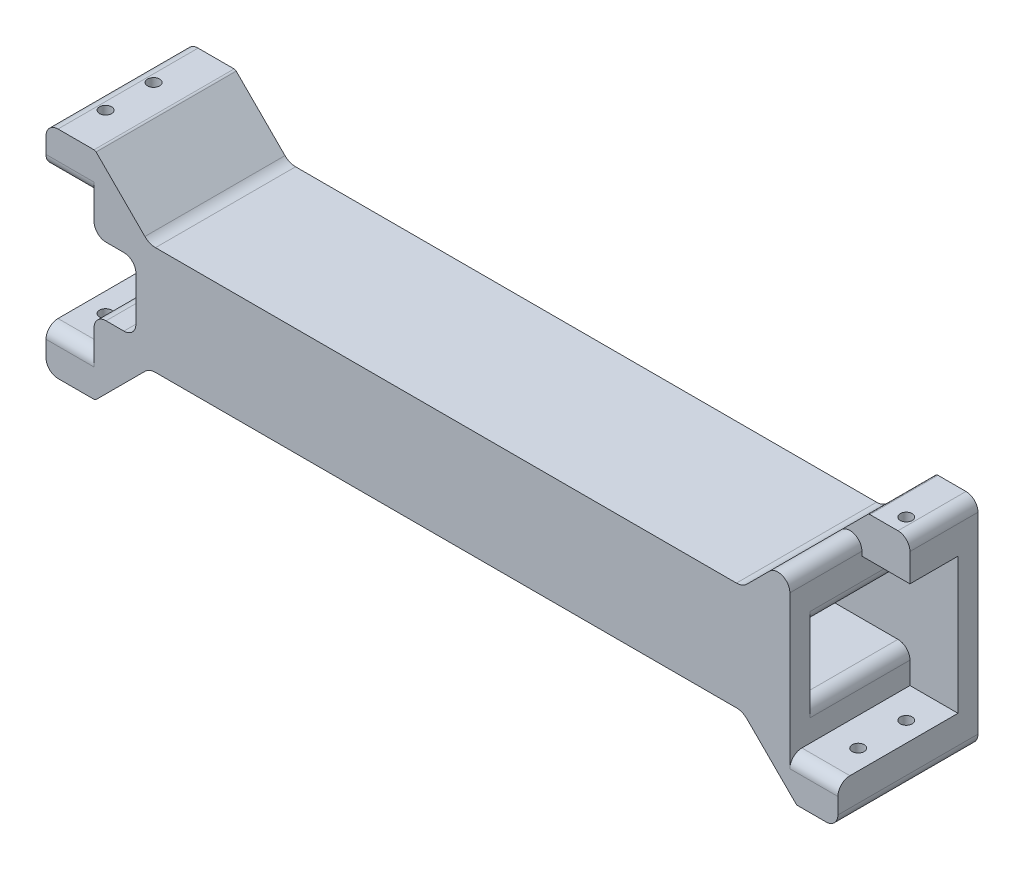
SolidWorks part; units mm, degrees
ref_plane "前视基准面" through (0, 0, 0) normal (0, 0, 1) x (1, 0, 0)
ref_plane "上视基准面" through (0, 0, 0) normal (0, 1, 0) x (1, 0, 0)
ref_plane "右视基准面" through (0, 0, 0) normal (1, 0, 0) x (0, 0, -1)
other "Configuration Table"
sketch "草图1" plane through (0, 0, 0) normal (0, 0, 1) x (1, 0, 0)
  line L0 (49.1217, 60) -> (0, 60) construction
  line L1 (0, 60) -> (0, 57) construction
  line L2 (0, 57) -> (49.1217, 57) construction
  line L3 (63.9537, 46.7157) -> (51.7639, 58.9056) construction
  line L4 (49.6425, 56.7843) -> (61.8324, 44.5944) construction
  line L5 (49.1217, 3) -> (0, 3) construction
  line L6 (0, 3) -> (0, 0) construction
  line L7 (0, 0) -> (49.1217, 0) construction
  line L8 (61.8324, 15.4056) -> (49.6425, 3.2157) construction
  line L9 (51.7639, 1.0944) -> (63.9537, 13.2843) construction
  line L10 (64.4745, 43.5) -> (209.6217, 43.5) construction
  line L11 (209.6217, 46.5) -> (64.4745, 46.5) construction
  line L12 (212.2639, 44.5944) -> (224.4537, 56.7843) construction
  line L13 (222.3324, 58.9056) -> (210.1425, 46.7157) construction
  line L14 (224.9745, 57) -> (268.4745, 57) construction
  line L15 (268.4745, 57) -> (268.4745, 60) construction
  line L16 (268.4745, 60) -> (224.9745, 60) construction
  line L17 (64.4745, 13.5) -> (209.6217, 13.5) construction
  line L18 (209.6217, 16.5) -> (64.4745, 16.5) construction
  line L19 (210.1425, 13.2843) -> (222.3324, 1.0944) construction
  line L20 (224.4537, 3.2157) -> (212.2639, 15.4056) construction
  line L21 (224.9745, 0) -> (268.4745, 0) construction
  line L22 (268.4745, 0) -> (268.4745, 3) construction
  line L23 (268.4745, 3) -> (224.9745, 3) construction
  line L24 (49.1217, 60) -> (0, 60)
  line L25 (0, 60) -> (0, 57)
  line L26 (0, 57) -> (49.1217, 57)
  line L27 (63.9537, 46.7157) -> (51.7639, 58.9056)
  line L28 (49.6425, 56.7843) -> (61.8324, 44.5944)
  line L29 (49.1217, 3) -> (0, 3)
  line L30 (0, 3) -> (0, 0)
  line L31 (0, 0) -> (49.1217, 0)
  line L32 (61.8324, 15.4056) -> (49.6425, 3.2157)
  line L33 (51.7639, 1.0944) -> (63.9537, 13.2843)
  line L34 (64.4745, 43.5) -> (209.6217, 43.5)
  line L35 (209.6217, 46.5) -> (64.4745, 46.5)
  line L36 (212.2639, 44.5944) -> (224.4537, 56.7843)
  line L37 (222.3324, 58.9056) -> (210.1425, 46.7157)
  line L38 (224.9745, 57) -> (268.4745, 57)
  line L39 (268.4745, 57) -> (268.4745, 60)
  line L40 (268.4745, 60) -> (224.9745, 60)
  line L41 (64.4745, 13.5) -> (209.6217, 13.5)
  line L42 (209.6217, 16.5) -> (64.4745, 16.5)
  line L43 (210.1425, 13.2843) -> (222.3324, 1.0944)
  line L44 (224.4537, 3.2157) -> (212.2639, 15.4056)
  line L45 (224.9745, 0) -> (268.4745, 0)
  line L46 (268.4745, 0) -> (268.4745, 3)
  line L47 (268.4745, 3) -> (224.9745, 3)
  line L48 (234.9745, 3) -> (234.9745, 57)
  line L49 (37.1217, 3) -> (37.1217, 57)
  arc A0 (49.6425, 56.7843) -> (49.1217, 57) centre (49.1217, 56.2634) ccw construction
  arc A1 (51.7639, 58.9056) -> (49.1217, 60) centre (49.1217, 56.2634) ccw construction
  arc A2 (61.8324, 44.5944) -> (64.4745, 43.5) centre (64.4745, 47.2366) ccw construction
  arc A3 (63.9537, 46.7157) -> (64.4745, 46.5) centre (64.4745, 47.2366) ccw construction
  arc A4 (49.1217, 0) -> (51.7639, 1.0944) centre (49.1217, 3.7366) ccw construction
  arc A5 (49.1217, 3) -> (49.6425, 3.2157) centre (49.1217, 3.7366) ccw construction
  arc A6 (64.4745, 13.5) -> (63.9537, 13.2843) centre (64.4745, 12.7634) ccw construction
  arc A7 (64.4745, 16.5) -> (61.8324, 15.4056) centre (64.4745, 12.7634) ccw construction
  arc A8 (209.6217, 43.5) -> (212.2639, 44.5944) centre (209.6217, 47.2366) ccw construction
  arc A9 (209.6217, 46.5) -> (210.1425, 46.7157) centre (209.6217, 47.2366) ccw construction
  arc A10 (224.9745, 57) -> (224.4537, 56.7843) centre (224.9745, 56.2634) ccw construction
  arc A11 (224.9745, 60) -> (222.3324, 58.9056) centre (224.9745, 56.2634) ccw construction
  arc A12 (210.1425, 13.2843) -> (209.6217, 13.5) centre (209.6217, 12.7634) ccw construction
  arc A13 (212.2639, 15.4056) -> (209.6217, 16.5) centre (209.6217, 12.7634) ccw construction
  arc A14 (222.3324, 1.0944) -> (224.9745, 0) centre (224.9745, 3.7366) ccw construction
  arc A15 (224.4537, 3.2157) -> (224.9745, 3) centre (224.9745, 3.7366) ccw construction
  arc A16 (49.6425, 56.7843) -> (49.1217, 57) centre (49.1217, 56.2634) ccw
  arc A17 (51.7639, 58.9056) -> (49.1217, 60) centre (49.1217, 56.2634) ccw
  arc A18 (61.8324, 44.5944) -> (64.4745, 43.5) centre (64.4745, 47.2366) ccw
  arc A19 (63.9537, 46.7157) -> (64.4745, 46.5) centre (64.4745, 47.2366) ccw
  arc A20 (49.1217, 0) -> (51.7639, 1.0944) centre (49.1217, 3.7366) ccw
  arc A21 (49.1217, 3) -> (49.6425, 3.2157) centre (49.1217, 3.7366) ccw
  arc A22 (64.4745, 13.5) -> (63.9537, 13.2843) centre (64.4745, 12.7634) ccw
  arc A23 (64.4745, 16.5) -> (61.8324, 15.4056) centre (64.4745, 12.7634) ccw
  arc A24 (209.6217, 43.5) -> (212.2639, 44.5944) centre (209.6217, 47.2366) ccw
  arc A25 (209.6217, 46.5) -> (210.1425, 46.7157) centre (209.6217, 47.2366) ccw
  arc A26 (224.9745, 57) -> (224.4537, 56.7843) centre (224.9745, 56.2634) ccw
  arc A27 (224.9745, 60) -> (222.3324, 58.9056) centre (224.9745, 56.2634) ccw
  arc A28 (210.1425, 13.2843) -> (209.6217, 13.5) centre (209.6217, 12.7634) ccw
  arc A29 (212.2639, 15.4056) -> (209.6217, 16.5) centre (209.6217, 12.7634) ccw
  arc A30 (222.3324, 1.0944) -> (224.9745, 0) centre (224.9745, 3.7366) ccw
  arc A31 (224.4537, 3.2157) -> (224.9745, 3) centre (224.9745, 3.7366) ccw
  dimension "D1" = 10
  dimension "D2" = 12
extrude "凸台-拉伸1" add sketch "草图1" against normal blind 35 contours L44 A31 L47 L48 L38 A26 L36 A24 L34 A18 L28 A16 L26 L49 L29 A21 L32 A23 L42 A29 region at (135.3571, 30, 0)
sketch "草图2" plane through (37.1217, 0, 0) normal (-1, 0, 0) x (0, 0, 1)
  line L0 (-35, 43.5) -> (0, 43.5) construction
  line L1 (-35, 43.5) -> (0, 43.5)
  line L2 (-35, 16.5) -> (0, 16.5) construction
  line L3 (-35, 16.5) -> (0, 16.5)
  line L4 (-35, 43.5) -> (0, 16.5) construction
  line L5 (-35, 16.5) -> (0, 43.5) construction
  line L6 (0, 3) -> (0, 57) construction
  line L7 (-30, 38.5) -> (-5, 38.5)
  line L8 (-30, 38.5) -> (-30, 21.5)
  line L9 (-30, 21.5) -> (-5, 21.5)
  line L10 (-5, 38.5) -> (-5, 21.5)
  line L11 (-30, 38.5) -> (-5, 21.5) construction
  line L12 (-30, 21.5) -> (-5, 38.5) construction
  point P4 (-17.5, 30)
  dimension "D1" = 5
  dimension "D2" = 5
extrude "切除-拉伸1" cut sketch "草图2" against normal through all contours L10 L7 L8 L9 region at (37.1217, 30, -17.5)
sketch "草图3" plane through (37.1217, 0, 0) normal (-1, 0, 0) x (0, 0, 1)
  line L0 (-30, 52) -> (-30, 8)
  line L1 (-30, 8) -> (-5, 8)
  line L2 (-5, 8) -> (-5, 52)
  line L3 (-5, 52) -> (-30, 52)
  line L4 (0, 3) -> (0, 57)
  line L5 (0, 57) -> (-35, 57)
  line L6 (-35, 57) -> (-35, 3)
  line L7 (-35, 3) -> (0, 3)
  line L8 (0, 3) -> (0, 57)
  line L9 (0, 57) -> (-35, 57)
  line L10 (-35, 57) -> (-35, 3)
  line L11 (-35, 3) -> (0, 3)
  line L12 (-30, 47) -> (-5, 47)
  line L13 (-30, 13) -> (-5, 13)
  line M14 (-5, 21.5) -> (-30, 21.5)
  line M16 (-30, 38.5) -> (-5, 38.5)
  dimension "D3" = 5
  dimension "D4" = 5
  dimension "D1" = 0
  dimension "D2" = 5
extrude "切除-拉伸2" cut sketch "草图3" against normal blind 12 contours L12 L0 L2 M16 | L0 L13 L2 M14 region at (37.1217, 42.75, -17.5) region at (37.1217, 17.25, -17.5)
ref_plane "基准面1" through (136.0481, 0, 0) normal (-1, 0, 0) x (0, 0, 1)
mirror "镜向1" about plane through (136.0481, 0, 0) normal (-1, 0, 0) of "切除-拉伸2"
fillet "圆角1" radius 3 8 edges at (222.9745, 38.5, -17.5) (222.9745, 21.5, -17.5) (234.9745, 57, -17.5) (234.9745, 3, -17.5) (37.1217, 57, -17.5) (37.1217, 3, -17.5) (49.1217, 21.5, -17.5) (49.1217, 38.5, -17.5)
sketch "草图4" plane through (0, 57, 0) normal (0, 1, 0) x (1, 0, 0)
  circle A2 centre (42, 22) radius 1.5 construction
  circle A3 centre (42, 10) radius 1.5 construction
  circle A6 centre (42, 22) radius 1.5
  circle A7 centre (42, 10) radius 1.5
  circle A8 centre (230.0481, 22) radius 1.5 construction
  circle A9 centre (230.0481, 10) radius 1.5 construction
  circle A10 centre (230.0481, 22) radius 1.5
  circle A11 centre (230.0481, 10) radius 1.5
extrude "切除-拉伸3" cut sketch "草图4" against normal through all both and the other way through all
sketch "草图5" plane through (0, 0, -5) normal (0, 0, -1) x (-1, 0, 0)
  line L0 (-222.9745, 41.5) -> (-222.9745, 18.5)
  line L1 (-49.1217, 41.5) -> (-49.1217, 18.5)
  line L12 (-37.1217, 13) -> (-37.1217, 47)
  line L13 (-37.1217, 47) -> (-49.1217, 47)
  line L14 (-49.1217, 47) -> (-49.1217, 41.5)
  line L15 (-52.1217, 38.5) -> (-219.9745, 38.5)
  line L16 (-222.9745, 41.5) -> (-222.9745, 47)
  line L17 (-222.9745, 47) -> (-234.9745, 47)
  line L18 (-234.9745, 47) -> (-234.9745, 13)
  line L19 (-234.9745, 13) -> (-222.9745, 13)
  line L20 (-222.9745, 13) -> (-222.9745, 18.5)
  line L21 (-219.9745, 21.5) -> (-52.1217, 21.5)
  line L22 (-49.1217, 18.5) -> (-49.1217, 13)
  line L23 (-49.1217, 13) -> (-37.1217, 13)
  line L24 (-37.1217, 13) -> (-37.1217, 47)
  line L25 (-37.1217, 47) -> (-49.1217, 47)
  line L26 (-49.1217, 47) -> (-49.1217, 41.5)
  line L27 (-52.1217, 38.5) -> (-219.9745, 38.5)
  line L28 (-222.9745, 41.5) -> (-222.9745, 47)
  line L29 (-222.9745, 47) -> (-234.9745, 47)
  line L30 (-234.9745, 47) -> (-234.9745, 13)
  line L31 (-234.9745, 13) -> (-222.9745, 13)
  line L32 (-222.9745, 13) -> (-222.9745, 18.5)
  line L33 (-219.9745, 21.5) -> (-52.1217, 21.5)
  line L34 (-49.1217, 18.5) -> (-49.1217, 13)
  line L35 (-49.1217, 13) -> (-37.1217, 13)
  arc A4 (-52.1217, 38.5) -> (-49.1217, 41.5) centre (-52.1217, 41.5) ccw
  arc A5 (-222.9745, 41.5) -> (-219.9745, 38.5) centre (-219.9745, 41.5) ccw
  arc A6 (-219.9745, 21.5) -> (-222.9745, 18.5) centre (-219.9745, 18.5) ccw
  arc A7 (-49.1217, 18.5) -> (-52.1217, 21.5) centre (-52.1217, 18.5) ccw
  arc A8 (-52.1217, 38.5) -> (-49.1217, 41.5) centre (-52.1217, 41.5) ccw
  arc A9 (-222.9745, 41.5) -> (-219.9745, 38.5) centre (-219.9745, 41.5) ccw
  arc A10 (-219.9745, 21.5) -> (-222.9745, 18.5) centre (-219.9745, 18.5) ccw
  arc A11 (-49.1217, 18.5) -> (-52.1217, 21.5) centre (-52.1217, 18.5) ccw
  line M17 (-37.1217, 13) -> (-37.1217, 47)
  line M18 (-37.1217, 47) -> (-49.1217, 47)
  line M19 (-49.1217, 47) -> (-49.1217, 41.5)
  line M23 (-222.9745, 41.5) -> (-222.9745, 47)
  line M24 (-222.9745, 47) -> (-234.9745, 47)
  line M25 (-234.9745, 47) -> (-234.9745, 13)
  line M26 (-234.9745, 13) -> (-222.9745, 13)
  line M27 (-222.9745, 13) -> (-222.9745, 18.5)
  line M31 (-49.1217, 18.5) -> (-49.1217, 13)
  line M32 (-49.1217, 13) -> (-37.1217, 13)
  dimension "D1" = 0
extrude "切除-拉伸4" cut sketch "草图5" against normal blind 10 contours L0 M23 M24 M25 M26 M27 | L1 M19 M31 M32 M17 M18 region at (228.9745, 30, -5) region at (43.1217, 30, -5)
fillet "圆角2" radius 3 4 edges at (228.9745, 13, 0) (228.9745, 47, 0) (43.1217, 13, 0) (43.1217, 47, 0)
sketch "草图6" plane through (0, 16.5, 0) normal (0, -1, 0) x (1, 0, 0)
  line L0 (106.0481, -17.5) -> (166.0481, -17.5) construction
  line L1 (136.0481, 19.25) -> (136.0481, -19.25) construction
  line L2 (106.0481, -9.5) -> (166.0481, -9.5)
  line L3 (106.0481, -25.5) -> (166.0481, -25.5)
  line L4 (136.0481, 0) -> (136.0481, -35)
  line L5 (209.6217, 0) -> (64.4745, 0) construction
  line L6 (209.6217, -35) -> (64.4745, -35) construction
  arc A0 (106.0481, -9.5) -> (106.0481, -25.5) centre (106.0481, -17.5) ccw
  arc A1 (166.0481, -25.5) -> (166.0481, -9.5) centre (166.0481, -17.5) ccw
  point P4 (136.0481, -17.5)
  dimension "D2" = 8
  dimension "D1" = 60
extrude "切除-拉伸5" [suppressed] cut sketch "草图6" against normal through all contours L3 A1 L2 L4 | L2 A0 L3 L4
sketch "草图7" plane through (0, 0, 0) normal (0, 0, 1) x (1, 0, 0)
  line L0 (234.9745, 47) -> (234.9745, 50) construction
  line L1 (222.9745, 47) -> (222.9745, 50) construction
  line L2 (222.9745, 47) -> (234.9745, 47) construction
  line L3 (49.1217, 50) -> (49.1217, 10) construction
  line L4 (49.1217, 10) -> (37.1217, 10) construction
  line L5 (37.1217, 10) -> (37.1217, 6) construction
  line L6 (40.1217, 3) -> (49.1217, 3) construction
  line L7 (49.6425, 3.2157) -> (61.8324, 15.4056) construction
  line L8 (64.4745, 16.5) -> (209.6217, 16.5) construction
  line L9 (212.2639, 15.4056) -> (224.4537, 3.2157) construction
  line L10 (224.9745, 3) -> (231.9745, 3) construction
  line L11 (234.9745, 6) -> (234.9745, 10) construction
  line L12 (234.9745, 10) -> (222.9745, 10) construction
  line L13 (222.9745, 10) -> (222.9745, 50) construction
  line L14 (234.9745, 50) -> (234.9745, 54) construction
  line L15 (231.9745, 57) -> (224.9745, 57) construction
  line L16 (224.4537, 56.7843) -> (212.2639, 44.5944) construction
  line L17 (209.6217, 43.5) -> (64.4745, 43.5) construction
  line L18 (61.8324, 44.5944) -> (49.6425, 56.7843) construction
  line L19 (49.1217, 57) -> (40.1217, 57) construction
  line L20 (37.1217, 54) -> (37.1217, 50) construction
  line L21 (37.1217, 50) -> (49.1217, 50) construction
  line L22 (234.9745, 47) -> (234.9745, 50)
  line L23 (222.9745, 47) -> (222.9745, 50)
  line L24 (222.9745, 47) -> (234.9745, 47)
  line L25 (49.1217, 50) -> (49.1217, 10)
  line L26 (49.1217, 10) -> (37.1217, 10)
  line L27 (37.1217, 10) -> (37.1217, 6)
  line L28 (40.1217, 3) -> (49.1217, 3)
  line L29 (49.6425, 3.2157) -> (61.8324, 15.4056)
  line L30 (64.4745, 16.5) -> (209.6217, 16.5)
  line L31 (212.2639, 15.4056) -> (224.4537, 3.2157)
  line L32 (224.9745, 3) -> (231.9745, 3)
  line L33 (234.9745, 6) -> (234.9745, 10)
  line L34 (234.9745, 10) -> (222.9745, 10)
  line L35 (222.9745, 10) -> (222.9745, 50)
  line L36 (234.9745, 50) -> (234.9745, 54)
  line L37 (231.9745, 57) -> (224.9745, 57)
  line L38 (224.4537, 56.7843) -> (212.2639, 44.5944)
  line L39 (209.6217, 43.5) -> (64.4745, 43.5)
  line L40 (61.8324, 44.5944) -> (49.6425, 56.7843)
  line L41 (49.1217, 57) -> (40.1217, 57)
  line L42 (37.1217, 54) -> (37.1217, 50)
  line L43 (37.1217, 50) -> (49.1217, 50)
  line L44 (222.9745, 50) -> (222.9745, 55.3051)
  arc A0 (37.1217, 6) -> (40.1217, 3) centre (40.1217, 6) ccw construction
  arc A1 (49.1217, 3) -> (49.6425, 3.2157) centre (49.1217, 3.7366) ccw construction
  arc A2 (64.4745, 16.5) -> (61.8324, 15.4056) centre (64.4745, 12.7634) ccw construction
  arc A3 (212.2639, 15.4056) -> (209.6217, 16.5) centre (209.6217, 12.7634) ccw construction
  arc A4 (224.4537, 3.2157) -> (224.9745, 3) centre (224.9745, 3.7366) ccw construction
  arc A5 (231.9745, 3) -> (234.9745, 6) centre (231.9745, 6) ccw construction
  arc A6 (234.9745, 54) -> (231.9745, 57) centre (231.9745, 54) ccw construction
  arc A7 (224.9745, 57) -> (224.4537, 56.7843) centre (224.9745, 56.2634) ccw construction
  arc A8 (209.6217, 43.5) -> (212.2639, 44.5944) centre (209.6217, 47.2366) ccw construction
  arc A9 (61.8324, 44.5944) -> (64.4745, 43.5) centre (64.4745, 47.2366) ccw construction
  arc A10 (49.6425, 56.7843) -> (49.1217, 57) centre (49.1217, 56.2634) ccw construction
  arc A11 (40.1217, 57) -> (37.1217, 54) centre (40.1217, 54) ccw construction
  arc A12 (37.1217, 6) -> (40.1217, 3) centre (40.1217, 6) ccw
  arc A13 (49.1217, 3) -> (49.6425, 3.2157) centre (49.1217, 3.7366) ccw
  arc A14 (64.4745, 16.5) -> (61.8324, 15.4056) centre (64.4745, 12.7634) ccw
  arc A15 (212.2639, 15.4056) -> (209.6217, 16.5) centre (209.6217, 12.7634) ccw
  arc A16 (224.4537, 3.2157) -> (224.9745, 3) centre (224.9745, 3.7366) ccw
  arc A17 (231.9745, 3) -> (234.9745, 6) centre (231.9745, 6) ccw
  arc A18 (234.9745, 54) -> (231.9745, 57) centre (231.9745, 54) ccw
  arc A19 (224.9745, 57) -> (224.4537, 56.7843) centre (224.9745, 56.2634) ccw
  arc A20 (209.6217, 43.5) -> (212.2639, 44.5944) centre (209.6217, 47.2366) ccw
  arc A21 (61.8324, 44.5944) -> (64.4745, 43.5) centre (64.4745, 47.2366) ccw
  arc A22 (49.6425, 56.7843) -> (49.1217, 57) centre (49.1217, 56.2634) ccw
  arc A23 (40.1217, 57) -> (37.1217, 54) centre (40.1217, 54) ccw
  line M17 (222.9745, 10) -> (222.9745, 50)
  line M18 (222.9745, 50) -> (234.9745, 50)
  line M19 (234.9745, 50) -> (234.9745, 54)
  arc M20 (234.9745, 54) -> (231.9745, 57) centre (231.9745, 54) ccw
  line M21 (231.9745, 57) -> (224.9745, 57)
  arc M22 (224.9745, 57) -> (224.4537, 56.7843) centre (224.9745, 56.2634) ccw
  line M23 (224.4537, 56.7843) -> (212.2639, 44.5944)
extrude "切除-拉伸6" cut sketch "草图7" against normal blind 18 contours L24 L22 M17 M18 | L44 M18 M19 M20 M21 M22 M23 region at (228.9745, 48.5, 0) region at (228.9443, 53.3794, 0)
fillet "圆角3" radius 3 1 edges at (222.9745, 55.3051, -9)
sketch "草图8" plane through (0, 0, -30) normal (0, 0, 1) x (1, 0, 0)
  line L0 (222.9745, 41.5) -> (222.9745, 18.5)
  line L1 (49.1217, 41.5) -> (49.1217, 18.5)
  line L12 (37.1217, 47) -> (37.1217, 13)
  line L13 (37.1217, 13) -> (49.1217, 13)
  line L14 (49.1217, 13) -> (49.1217, 18.5)
  line L15 (52.1217, 21.5) -> (219.9745, 21.5)
  line L16 (222.9745, 18.5) -> (222.9745, 13)
  line L17 (222.9745, 13) -> (234.9745, 13)
  line L18 (234.9745, 13) -> (234.9745, 47)
  line L19 (234.9745, 47) -> (222.9745, 47)
  line L20 (222.9745, 47) -> (222.9745, 41.5)
  line L21 (219.9745, 38.5) -> (52.1217, 38.5)
  line L22 (49.1217, 41.5) -> (49.1217, 47)
  line L23 (49.1217, 47) -> (37.1217, 47)
  line L24 (37.1217, 47) -> (37.1217, 13)
  line L25 (37.1217, 13) -> (49.1217, 13)
  line L26 (49.1217, 13) -> (49.1217, 18.5)
  line L27 (52.1217, 21.5) -> (219.9745, 21.5)
  line L28 (222.9745, 18.5) -> (222.9745, 13)
  line L29 (222.9745, 13) -> (234.9745, 13)
  line L30 (234.9745, 13) -> (234.9745, 47)
  line L31 (234.9745, 47) -> (222.9745, 47)
  line L32 (222.9745, 47) -> (222.9745, 41.5)
  line L33 (219.9745, 38.5) -> (52.1217, 38.5)
  line L34 (49.1217, 41.5) -> (49.1217, 47)
  line L35 (49.1217, 47) -> (37.1217, 47)
  arc A4 (52.1217, 21.5) -> (49.1217, 18.5) centre (52.1217, 18.5) ccw
  arc A5 (222.9745, 18.5) -> (219.9745, 21.5) centre (219.9745, 18.5) ccw
  arc A6 (219.9745, 38.5) -> (222.9745, 41.5) centre (219.9745, 41.5) ccw
  arc A7 (49.1217, 41.5) -> (52.1217, 38.5) centre (52.1217, 41.5) ccw
  arc A8 (52.1217, 21.5) -> (49.1217, 18.5) centre (52.1217, 18.5) ccw
  arc A9 (222.9745, 18.5) -> (219.9745, 21.5) centre (219.9745, 18.5) ccw
  arc A10 (219.9745, 38.5) -> (222.9745, 41.5) centre (219.9745, 41.5) ccw
  arc A11 (49.1217, 41.5) -> (52.1217, 38.5) centre (52.1217, 41.5) ccw
  line M17 (37.1217, 47) -> (37.1217, 13)
  line M18 (37.1217, 13) -> (49.1217, 13)
  line M19 (49.1217, 13) -> (49.1217, 18.5)
  line M31 (49.1217, 41.5) -> (49.1217, 47)
  line M32 (49.1217, 47) -> (37.1217, 47)
  dimension "D1" = 0
extrude "切除-拉伸8" cut sketch "草图8" against normal blind 10 contours L1 M31 M32 M17 M18 M19 region at (43.1217, 30, -30)
fillet "圆角4" radius 3 2 edges at (43.1217, 13, -35) (43.1217, 47, -35)
sketch "草图9" plane through (0, 0, -35) normal (0, 0, -1) x (-1, 0, 0)
  circle A0 centre (-55.1912, 25) radius 1.5 construction
  circle A1 centre (-55.1912, 25) radius 1.5
  circle A2 centre (-55.1912, 35) radius 1.5 construction
  circle A3 centre (-55.1912, 35) radius 1.5
extrude "切除-拉伸9" cut sketch "草图9" against normal blind 8
sketch "草图10" plane through (0, 0, -5) normal (0, 0, -1) x (-1, 0, 0)
  line L0 (-59.5869, 38.5) -> (-59.5869, 21.5)
  line L4 (-222.9745, 41.5) -> (-222.9745, 18.5)
  line L5 (-219.9745, 21.5) -> (-52.1217, 21.5)
  line L6 (-49.1217, 18.5) -> (-49.1217, 41.5)
  line L7 (-52.1217, 38.5) -> (-219.9745, 38.5)
  line L8 (-222.9745, 41.5) -> (-222.9745, 18.5)
  line L9 (-219.9745, 21.5) -> (-52.1217, 21.5)
  line L10 (-49.1217, 18.5) -> (-49.1217, 41.5)
  line L11 (-52.1217, 38.5) -> (-219.9745, 38.5)
  arc A4 (-222.9745, 41.5) -> (-219.9745, 38.5) centre (-219.9745, 41.5) ccw
  arc A5 (-219.9745, 21.5) -> (-222.9745, 18.5) centre (-219.9745, 18.5) ccw
  arc A6 (-49.1217, 18.5) -> (-52.1217, 21.5) centre (-52.1217, 18.5) ccw
  arc A7 (-52.1217, 38.5) -> (-49.1217, 41.5) centre (-52.1217, 41.5) ccw
  arc A8 (-222.9745, 41.5) -> (-219.9745, 38.5) centre (-219.9745, 41.5) ccw
  arc A9 (-219.9745, 21.5) -> (-222.9745, 18.5) centre (-219.9745, 18.5) ccw
  arc A10 (-49.1217, 18.5) -> (-52.1217, 21.5) centre (-52.1217, 18.5) ccw
  arc A11 (-52.1217, 38.5) -> (-49.1217, 41.5) centre (-52.1217, 41.5) ccw
  line M12 (-219.9745, 21.5) -> (-52.1217, 21.5)
  arc M13 (-52.1217, 21.5) -> (-49.1217, 18.5) centre (-52.1217, 18.5) cw
  line M14 (-49.1217, 18.5) -> (-49.1217, 41.5)
  arc M15 (-49.1217, 41.5) -> (-52.1217, 38.5) centre (-52.1217, 41.5) cw
  line M16 (-52.1217, 38.5) -> (-219.9745, 38.5)
  dimension "D1" = 0
extrude "切除-拉伸10" cut sketch "草图10" against normal blind 8 contours L0 M16 M12 M13 M14 M15 region at (54.2573, 30, -5)
fillet "圆角5" radius 3 2 edges at (59.5869, 21.5, -2.5) (59.5869, 38.5, -2.5)
